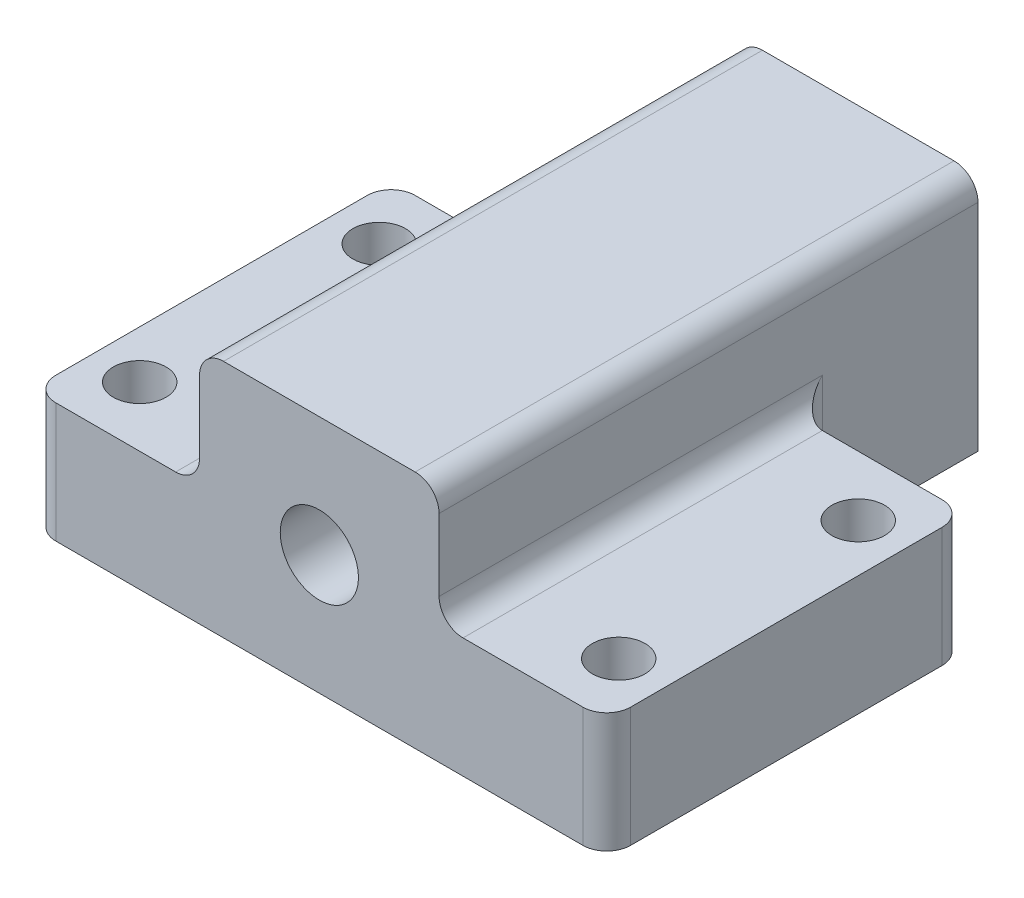
SolidWorks part; units mm, degrees
ref_plane "Front Plane" through (0, 0, 0) normal (0, 0, 1) x (1, 0, 0)
ref_plane "Top Plane" through (0, 0, 0) normal (0, 1, 0) x (1, 0, 0)
ref_plane "Right Plane" through (0, 0, 0) normal (1, 0, 0) x (0, 0, -1)
sketch "Sketch1" plane through (0, 0, 0) normal (0, 1, 0) x (1, 0, 0)
  line L0 (0, 0) -> (0, 15) construction
  line L1 (-24, -15) -> (24, -15)
  line L2 (-24, -15) -> (-24, 15)
  line L3 (-24, 15) -> (24, 15)
  line L4 (24, -15) -> (24, 15)
  line L5 (-24, -10) -> (24, -10) construction
  line L6 (-24, 10) -> (24, 10) construction
  line L7 (-20, -15) -> (-20, 10) construction
  line L8 (20, -15) -> (20, 10) construction
  line L15 (0, 0) -> (24, 0) construction
  circle A0 centre (-20, 10) radius 2.2
  circle A1 centre (20, 10) radius 2.2
  circle A2 centre (20, -10) radius 2.2
  circle A3 centre (-20, -10) radius 2.2
  dimension "D6" = 4.4
  dimension "D1" = 48
  dimension "D2" = 30
  dimension "D3" = 20
  dimension "D4" = 40
  dimension "D5" = 5
extrude "Boss-Extrude1" add sketch "Sketch1" along normal blind 10
sketch "Sketch3" plane through (0, 0, -15) normal (0, 0, -1) x (-1, 0, 0)
  line L0 (-24, 0) -> (24, 0) construction
  line L11 (0, 0) -> (0, 20) construction
  line L12 (-10, 0) -> (10, 0)
  line L13 (-10, 0) -> (-10, 20)
  line L14 (-10, 20) -> (10, 20)
  line L15 (10, 0) -> (10, 20)
  dimension "D1" = 20
  dimension "D2" = 20
extrude "Boss-Extrude2" add sketch "Sketch3" against normal up to surface (30 mm away) and the other way blind 15 up to face at (0, 5, 15)
sketch "Sketch4" plane through (0, 0, -30) normal (0, 0, -1) x (-1, 0, 0)
  line L0 (-24, 0) -> (-10, 0) construction
  line L1 (-6.5, 13.7528) -> (-6.5, 6.2472)
  line L2 (-6.5, 6.2472) -> (0, 2.4944)
  line L3 (0, 2.4944) -> (6.5, 6.2472)
  line L4 (6.5, 6.2472) -> (6.5, 13.7528)
  line L5 (6.5, 13.7528) -> (0, 17.5056)
  line L6 (0, 17.5056) -> (-6.5, 13.7528)
  circle A0 centre (0, 10) radius 6.5 construction
  point P1 (-3.013, 15.1976)
  dimension "D1" = 13
  dimension "D2" = 10
extrude "Cut-Extrude1" cut sketch "Sketch4" against normal up to surface (30 mm away) up to plane "Front Plane"
sketch "Sketch5" plane through (0, 0, -15) normal (0, 0, -1) x (-1, 0, 0)
  line L1 (-6.5, 13.7528) -> (6.5, 6.2472) construction
  line L2 (-6.5, 6.2472) -> (6.5, 13.7528) construction
  line L3 (0, 20) -> (0, 2.4944) construction
  line L7 (0, 17.5056) -> (-6.5, 13.7528)
  line L8 (-6.5, 13.7528) -> (-6.5, 6.2472)
  line L9 (-6.5, 6.2472) -> (0, 2.4944)
  line L10 (0, 2.4944) -> (6.5, 6.2472)
  line L11 (6.5, 6.2472) -> (6.5, 13.7528)
  line L12 (6.5, 13.7528) -> (0, 17.5056)
  line L13 (0, 17.5056) -> (-6.5, 13.7528) construction
  line L14 (-6.5, 13.7528) -> (-6.5, 6.2472) construction
  line L15 (-6.5, 6.2472) -> (0, 2.4944) construction
  line L16 (0, 2.4944) -> (6.5, 6.2472) construction
  line L17 (6.5, 6.2472) -> (6.5, 13.7528) construction
  line L18 (6.5, 13.7528) -> (0, 17.5056) construction
  circle A0 centre (0, 10) radius 3.2639
  dimension "D2" = 6.5278
  dimension "D1" = 0
extrude "Cut-Extrude2" cut sketch "Sketch5" against normal through all
fillet "Fillet2" radius 2 10 edges at (-24, 5, 15) (-24, 5, -15) (24, 5, 15) (24, 5, -15) (-10, 10, 0) (-10, 20, -7.5) (10, 20, -7.5) (10, 10, 0) (-10, 5, -15) (10, 5, -15)
